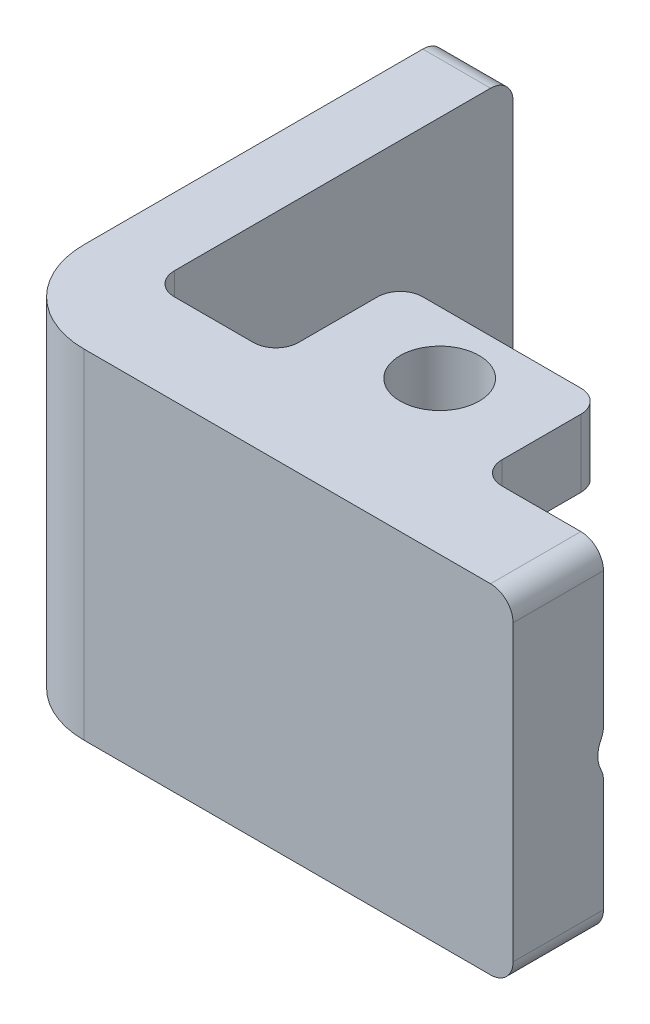
SolidWorks part; units mm, degrees
ref_plane "Plan de face" through (0, 0, 0) normal (0, 0, 1) x (1, 0, 0)
ref_plane "Plan de dessus" through (0, 0, 0) normal (0, 1, 0) x (1, 0, 0)
ref_plane "Plan de droite" through (0, 0, 0) normal (1, 0, 0) x (0, 0, -1)
sketch "Esquisse1" plane through (0, 0, 0) normal (0, 0, 1) x (1, 0, 0)
  line L2 (-10, -7.5) -> (10, -7.5)
  line L3 (-10, -7.5) -> (-10, 7.5)
  line L4 (-10, 7.5) -> (10, 7.5)
  line L5 (10, -7.5) -> (10, 7.5)
  point P0 (-10, 0)
  point P3 (0, 7.5)
  dimension "D1" = 20
  dimension "D4" = 15
extrude "Boss.-Extru.1" add sketch "Esquisse1" along normal blind 4
sketch "Esquisse3" plane through (0, 0, 0) normal (0, 0, -1) x (-1, 0, 0)
  line L5 (-10, 7.5) -> (10, 7.5) construction
  line L6 (-4.5, 7.5) -> (4.5, 7.5)
  line L8 (-4.5, 7.5) -> (-4.5, 4.5)
  line L9 (-4.5, 4.5) -> (4.5, 4.5)
  line L10 (4.5, 7.5) -> (4.5, 4.5)
  point P6 (0, 4.5)
  dimension "D1" = 3
  dimension "D2" = 9
extrude "Boss.-Extru.2" add sketch "Esquisse3" along normal blind 5.5
sketch "Esquisse4" plane through (0, 7.5, 0) normal (0, 1, 0) x (1, 0, 0)
  line L0 (0, 0) -> (0, 2.75) construction
  line L1 (0, 2.75) -> (0, 5.5) construction
  line L2 (-4.5, 5.5) -> (4.5, 5.5) construction
  circle A0 centre (0, 2.75) radius 1.75
  dimension "D1" = 3.5
extrude "Enlèv. mat.-Extru.1" cut sketch "Esquisse4" against normal up to next
sketch "Esquisse6" plane through (-10, 0, 0) normal (-1, 0, 0) x (0, 0, 1)
  line L0 (4, 7.5) -> (0, 7.5) construction
  line L1 (4, -7.5) -> (-16, -7.5)
  line L2 (4, -7.5) -> (4, 7.5)
  line L3 (4, 7.5) -> (-16, 7.5)
  line L4 (-16, -7.5) -> (-16, 7.5)
  line L5 (4, 7.5) -> (4, -7.5) construction
  line L6 (-11, -0.5) -> (-1, -0.5) construction
  line L7 (-1, -0.5) -> (4, -0.5) construction
  line L8 (-11, -0.5) -> (-16, -0.5) construction
  circle A0 centre (-11, -0.5) radius 1.25
  circle A1 centre (-1, -0.5) radius 1.25
  point P14 (0, 0)
  point P16 (0, 0)
  line M10 (0, 7.5) -> (0, -7.5)
  dimension "D1" = 2.5
  dimension "D2" = 10
  dimension "D3" = 20
  dimension "D4" = 7
extrude "Boss.-Extru.4" add sketch "Esquisse6" along normal blind 3
extrude "Enlèv. mat.-Extru.5" cut sketch "Esquisse6<3>" against normal up to next contours A1 M10 region at (-10, -0.5, 0.1009)
sketch "Esquisse6<3>" plane through (-10, 0, 0) normal (-1, 0, 0) x (0, 0, 1) same geometry as "Esquisse6"
fillet "Congé1" radius 1 13 edges at (4.5, 6, 0) (-4.5, 6, 0) (4.5, 6, -5.5) (-4.5, 6, -5.5) (-10, -0.5, -2.25) (10, -7.5, 2) (-11.5, -7.5, -16) (-11.5, 7.5, -16) (10, 7.5, 2) (-10, 3.875, 0) (-10, -4.375, 0) (0, 0.25, 0) (0, -1.25, 0)
fillet "Congé2" radius 4 1 edges at (-13, 0, 4)
